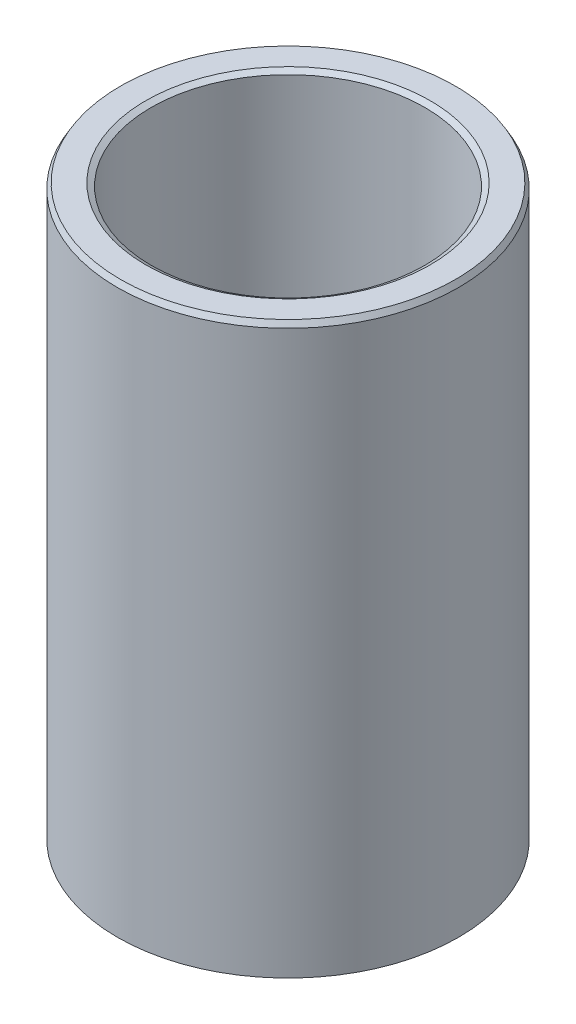
SolidWorks part; units mm, degrees
ref_plane "Front Plane" through (0, 0, 0) normal (0, 0, 1) x (1, 0, 0)
ref_plane "Top Plane" through (0, 0, 0) normal (0, 1, 0) x (1, 0, 0)
ref_plane "Right Plane" through (0, 0, 0) normal (1, 0, 0) x (0, 0, -1)
sketch "Sketch1" plane through (0, 0, 0) normal (0, 1, 0) x (1, 0, 0)
  circle A0 centre (0, 0) radius 47.5
  dimension "SLEEVE_OD" = 95
extrude "Boss-Extrude1" add sketch "Sketch1" along normal blind 159.0286
sketch "Sketch2" plane through (0, 0, 0) normal (0, 1, 0) x (1, 0, 0)
  circle A0 centre (0, 0) radius 38.0895
  dimension "BORE_D" = 76.179
extrude "Cut-Extrude1" cut sketch "Sketch2" along normal through all
chamfer "Chamfer1" distance 1.5084 angle 30 4 edges at (0, 159.0286, 38.0895) (0, 0, 38.0895) (0, 0, 47.5) (0, 159.0286, 47.5) first distance on face at (0, 159.0286, 38.0895) first distance on face at (0, 0, 38.0895) first distance on face at (0, 159.0286, 47.5)
